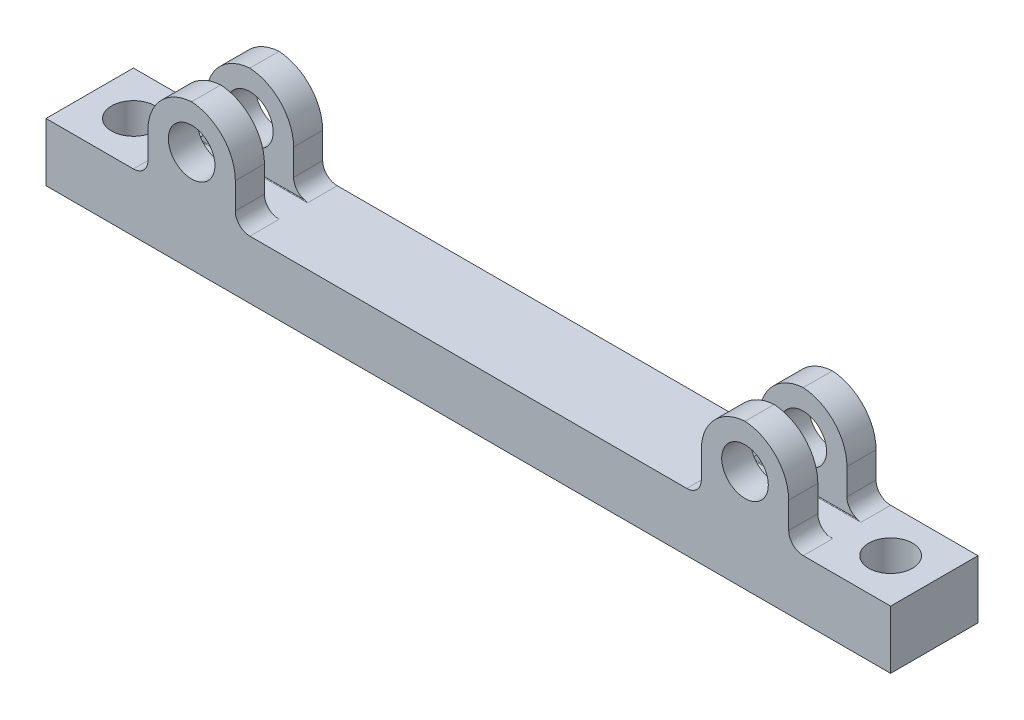
SolidWorks part; units mm, degrees
ref_plane "Front Plane" through (0, 0, 0) normal (0, 0, 1) x (1, 0, 0)
ref_plane "Top Plane" through (0, 0, 0) normal (0, 1, 0) x (1, 0, 0)
ref_plane "Right Plane" through (0, 0, 0) normal (1, 0, 0) x (0, 0, -1)
sketch "Sketch1" plane through (0, 0, 0) normal (0, 0, 1) x (1, 0, 0)
  line L0 (0, 0) -> (0, 12.7)
  line L1 (0, 0) -> (55.88, 0)
  line L5 (0, 12.7) -> (7.62, 12.7)
  line L6 (7.62, 12.7) -> (7.62, 5.08)
  line L7 (7.62, 5.08) -> (48.26, 5.08)
  line L8 (48.26, 5.08) -> (48.26, 12.7)
  line L9 (48.26, 12.7) -> (55.88, 12.7)
  line L10 (55.88, 12.7) -> (55.88, 0)
  circle A0 centre (3.81, 8.89) radius 2.032
  circle A1 centre (52.07, 8.89) radius 2.032
  point P17 (3.81, 12.7)
  dimension "D6" = 4.064
  dimension "D7" = 4.064
  dimension "D1" = 55.88
  dimension "D2" = 7.62
  dimension "D3" = 7.62
  dimension "D4" = 7.62
  dimension "D5" = 5.08
  dimension "D8" = 48.26
  dimension "D9" = 3.81
  dimension "D10" = 3.81
extrude "Boss-Extrude1" add sketch "Sketch1" against normal blind 7.62
sketch "Sketch3" plane through (55.88, 0, 0) normal (1, 0, 0) x (0, 0, -1)
  line L0 (7.62, 12.7) -> (0, 12.7) construction
  line L1 (2.54, 12.7) -> (5.08, 12.7)
  line L2 (2.54, 12.7) -> (2.54, 5.08)
  line L3 (2.54, 5.08) -> (5.08, 5.08)
  line L4 (5.08, 12.7) -> (5.08, 5.08)
  line L5 (7.62, 0) -> (0, 0) construction
  point P6 (3.81, 12.7)
  point P9 (3.81, 0)
  dimension "D1" = 7.62
  dimension "D2" = 2.54
extrude "Cut-Extrude1" cut sketch "Sketch3" against normal blind 55.88
fillet "Fillet2" radius 4.064 8 edges at (48.26, 12.7, -6.35) (48.26, 12.7, -1.27) (7.62, 12.7, -6.35) (7.62, 12.7, -1.27) (55.88, 12.7, -1.27) (55.88, 12.7, -6.35) (0, 12.7, -6.35) (0, 12.7, -1.27)
sketch "Sketch5" plane through (0, 0, 0) normal (0, 1, 0) x (1, 0, 0)
  line L1 (0, 0) -> (-8.89, 0)
  line L2 (0, 0) -> (0, 7.62)
  line L3 (0, 7.62) -> (-8.89, 7.62)
  line L4 (-8.89, 0) -> (-8.89, 7.62)
  line L5 (55.88, 7.62) -> (64.77, 7.62)
  line L6 (55.88, 7.62) -> (55.88, 0)
  line L7 (55.88, 0) -> (64.77, 0)
  line L8 (64.77, 7.62) -> (64.77, 0)
  circle A0 centre (-5.08, 3.81) radius 1.905
  circle A1 centre (60.96, 3.81) radius 1.905
  point P19 (-8.89, 3.81)
  point P21 (64.77, 3.81)
  dimension "D3" = 3.81
  dimension "D4" = 3.81
  dimension "D1" = 8.89
  dimension "D2" = 8.89
extrude "Boss-Extrude2" add sketch "Sketch5" along normal blind 5.08
fillet "Fillet3" radius 1.27 8 edges at (0, 5.08, -6.35) (0, 5.08, -1.27) (48.26, 5.08, -6.35) (48.26, 5.08, -1.27) (55.88, 5.08, -6.35) (55.88, 5.08, -1.27) (7.62, 5.08, -6.35) (7.62, 5.08, -1.27)
fillet "Fillet4" radius 0.0508 4 edges at (52.07, 5.08, -5.08) (52.07, 5.08, -2.54) (3.81, 5.08, -2.54) (3.81, 5.08, -5.08)
